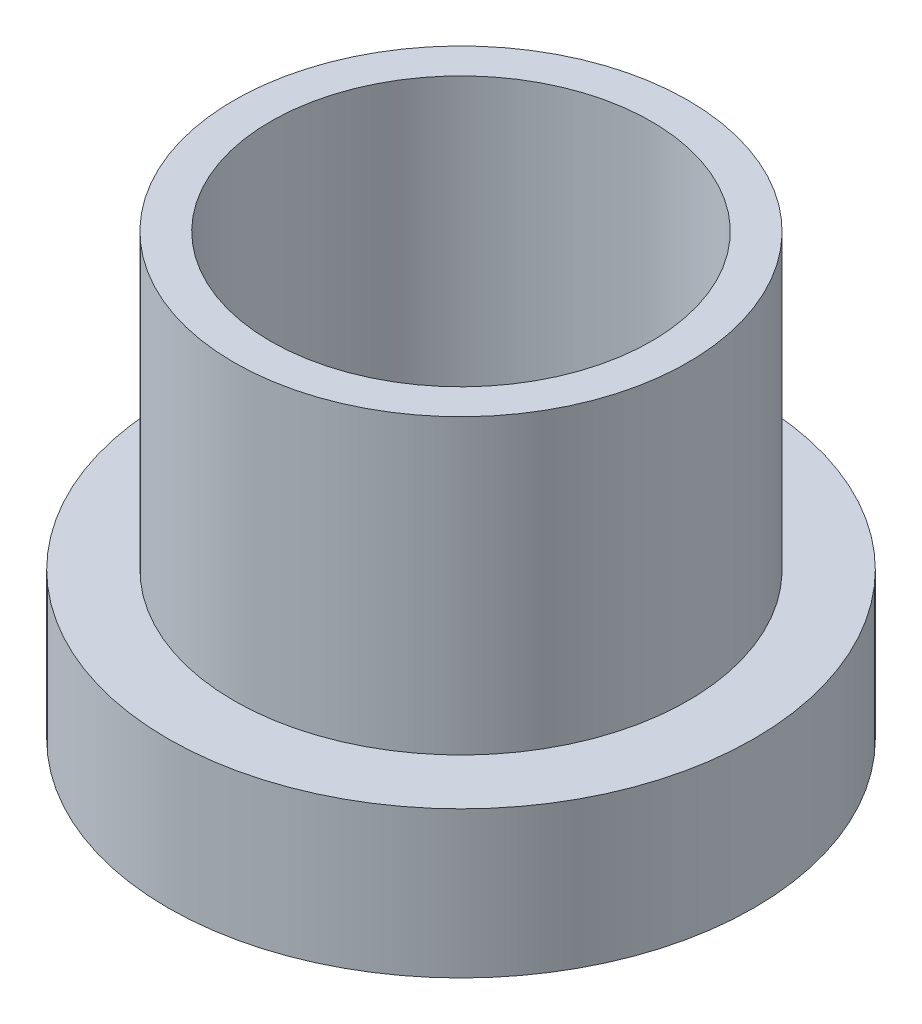
SolidWorks part; units mm, degrees
ref_plane "Front Plane" through (0, 0, 0) normal (0, 0, 1) x (1, 0, 0)
ref_plane "Top Plane" through (0, 0, 0) normal (0, 1, 0) x (1, 0, 0)
ref_plane "Right Plane" through (0, 0, 0) normal (1, 0, 0) x (0, 0, -1)
sketch "Sketch1" plane through (0, 0, 0) normal (0, 1, 0) x (1, 0, 0)
  circle A0 centre (0, 0) radius 2.6
  circle A1 centre (0, 0) radius 3.1
  dimension "D1" = 5.2
  dimension "D2" = 6.2
extrude "Boss-Extrude1" add sketch "Sketch1" along normal blind 6
sketch "Sketch2" plane through (0, 0, 0) normal (0, -1, 0) x (1, 0, 0)
  circle A0 centre (0, 0) radius 2.6
  circle A1 centre (0, 0) radius 4
  dimension "D1" = 8
  dimension "D2" = 5.2
extrude "Boss-Extrude2" add sketch "Sketch2" against normal blind 2
